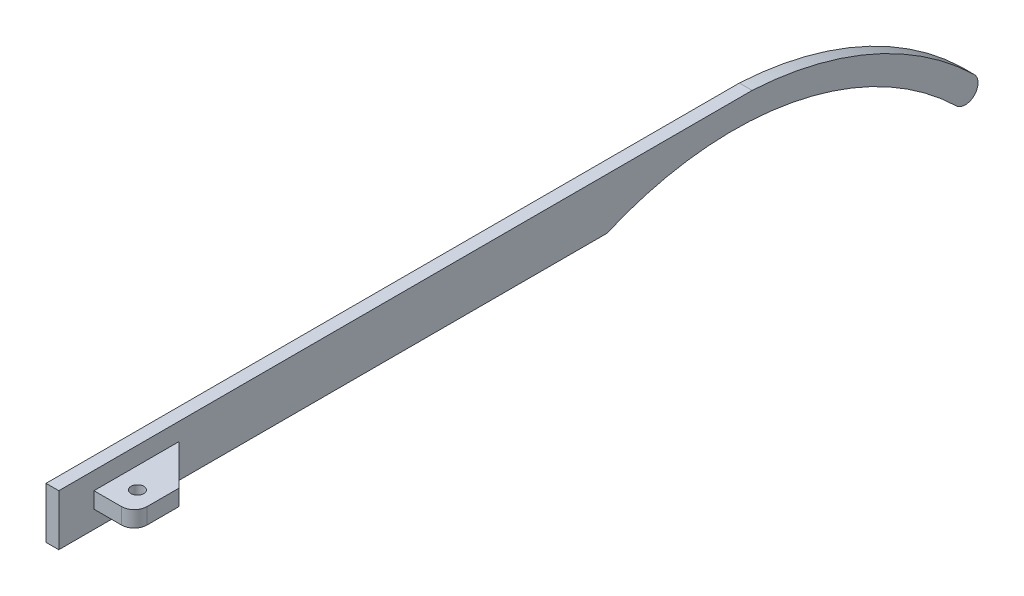
SolidWorks part; units mm, degrees
ref_plane "Front Plane" through (0, 0, 0) normal (0, 0, 1) x (1, 0, 0)
ref_plane "Top Plane" through (0, 0, 0) normal (0, 1, 0) x (1, 0, 0)
ref_plane "Right Plane" through (0, 0, 0) normal (1, 0, 0) x (0, 0, -1)
sketch "Sketch1" plane through (0, 0, 0) normal (1, 0, 0) x (0, 0, -1)
  line L1 (-70, 4) -> (70, 4)
  line L2 (-70, 4) -> (-70, -4)
  line L3 (-70, -4) -> (70, -4)
  line L4 (70, 4) -> (70, -4)
  line L5 (-70, 4) -> (70, -4) construction
  line L6 (-70, -4) -> (70, 4) construction
  point P0 (0, 0)
  dimension "D1" = 140
  dimension "D2" = 8
extrude "Boss-Extrude1" add sketch "Sketch1" along normal blind 2
sketch "Sketch3" plane through (2, 0, 0) normal (1, 0, 0) x (0, 0, -1)
  line L0 (-70, 4) -> (-70, -4) construction
  line L1 (-70, 1.25) -> (-63, 1.25)
  line L2 (-70, 1.25) -> (-70, -1.25)
  line L3 (-70, -1.25) -> (-63, -1.25)
  line L4 (-63, 1.25) -> (-63, -1.25)
  line L5 (70, 4) -> (-70, 4) construction
  line L6 (-70, -4) -> (70, -4) construction
  dimension "D1" = 2.75
  dimension "D2" = 2.75
  dimension "D3" = 7
extrude "Boss-Extrude2" add sketch "Sketch3" along normal blind 6.3
sketch "Sketch4" plane through (0, 1.25, 0) normal (0, 1, 0) x (1, 0, 0)
  line L1 (8.3, -70) -> (2, -70) construction
  line L2 (8.3, -63) -> (8.3, -70) construction
  circle A0 centre (5.3, -66.5) radius 1
  dimension "D1" = 2
  dimension "D2" = 3.5
  dimension "D3" = 3
extrude "Cut-Extrude1" cut sketch "Sketch4" against normal blind 4
sketch "Sketch6" plane through (2, 0, 0) normal (1, 0, 0) x (0, 0, -1)
  line L0 (-70, -1.25) -> (-70, -4) construction
  circle A0 centre (30, -49.921) radius 50
  dimension "D1" = 100
  dimension "D2" = 100
extrude "Cut-Extrude3" cut sketch "Sketch6" against normal blind 14
sketch "Sketch9" plane through (2, 0, 0) normal (1, 0, 0) x (0, 0, -1)
  line L0 (69.0932, -12.6689) -> (66.1974, -15.4283)
  line L1 (49.7803, -4) -> (58.4123, -4)
  arc A0 (66.1974, -15.4283) -> (49.7803, -4) centre (30, -49.921) ccw
  arc A1 (69.0932, -12.6689) -> (58.4123, -4) centre (30, -49.921) ccw
  dimension "D1" = 4
extrude "Boss-Extrude4" add sketch "Sketch9" against normal blind 2
sketch "Sketch10" plane through (2, 0, 0) normal (1, 0, 0) x (0, 0, -1)
  line L0 (30, 4.079) -> (98.6931, 13.3575)
  line L1 (98.6931, 13.3575) -> (83.7432, -55.1811)
  arc A0 (83.7432, -55.1811) -> (30, 4.079) centre (30, -49.921) ccw
extrude "Cut-Extrude5" cut sketch "Sketch10" against normal blind 2
fillet "Fillet6" radius 2 2 edges at (1, -15.4283, -66.1974) (1, -12.6689, -69.0932)
ref_plane "Plane1" through (-10, 0, 0) normal (-1, 0, 0) x (0, 0, 1)
fillet "Fillet7" radius 2 1 edges at (8.3, 0, 70)
sketch "Sketch11" plane through (0, 0, 70) normal (0, 0, 1) x (1, 0, 0)
  line L1 (0, 4) -> (2, 4)
  line L2 (0, 4) -> (0, -4)
  line L3 (0, -4) -> (2, -4)
  line L4 (2, 4) -> (2, -4)
extrude "Boss-Extrude5" add sketch "Sketch11" along normal blind 5.5
chamfer "Chamfer1" distance 6.3 angle 45 1 edges at (2, 0, 63)
